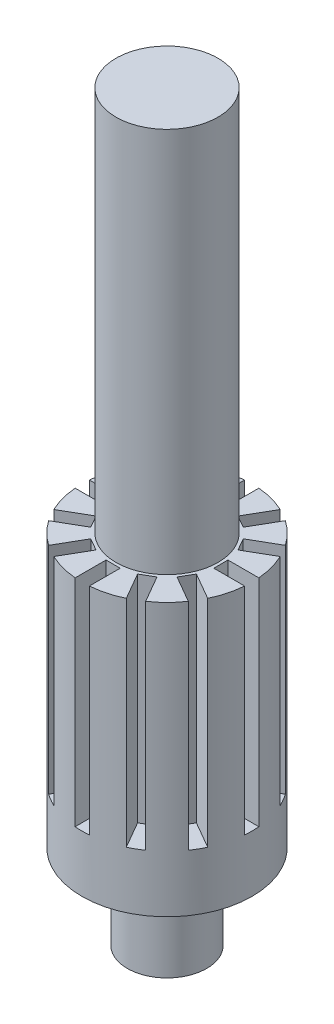
SolidWorks part; units mm, degrees
ref_plane "Front Plane" through (0, 0, 0) normal (0, 0, 1) x (1, 0, 0)
ref_plane "Top Plane" through (0, 0, 0) normal (0, 1, 0) x (1, 0, 0)
ref_plane "Right Plane" through (0, 0, 0) normal (1, 0, 0) x (0, 0, -1)
sketch "Sketch1" plane through (0, 0, 0) normal (0, 1, 0) x (1, 0, 0)
  circle A0 centre (0, 0) radius 15
  circle A1 centre (0, 0) radius 9
  point P4 (0, 0)
  dimension "D1" = 30
  dimension "D2" = 18
extrude "Boss-Extrude1" add sketch "Sketch1" against normal blind 48 contours A0 A1 | A1 region at (-14.5757, 0, 0) region at (0, 0, 0)
extrude "Boss-Extrude2" add sketch "Sketch1<4>" along normal blind 68 contours A1 region at (0, 0, 0)
sketch "Sketch1<4>" plane through (0, 0, 0) normal (0, 1, 0) x (1, 0, 0) same geometry as "Sketch1"
sketch "Sketch2" plane through (0, -48, 0) normal (0, -1, 0) x (1, 0, 0)
  circle A0 centre (0, 0) radius 7
  dimension "D1" = 14
extrude "Boss-Extrude3" add sketch "Sketch2" along normal blind 15
sketch "Sketch3" plane through (0, 0, 0) normal (0, 1, 0) x (1, 0, 0)
  line L1 (-1.25, 9.5) -> (1.25, 9.5)
  line L2 (-1.25, 9.5) -> (-1.25, 15.7102)
  line L3 (-1.25, 15.7102) -> (1.25, 15.7102)
  line L4 (1.25, 9.5) -> (1.25, 15.7102)
  point P4 (0, 9.5)
  point P6 (1.25, 15.7102)
  dimension "D1" = 2.5
  dimension "D2" = 9.5
extrude "Cut-Extrude1" cut sketch "Sketch3" against normal blind 38
pattern_circular "CirPattern1" count 12 over 360 about axis through (0, 0, 0) along (0, 1, 0) of "Cut-Extrude1"
sketch "Sketch4" plane through (0, -63, 0) normal (0, -1, 0) x (1, 0, 0)
  circle A0 centre (0, 0) radius 1.25
  dimension "D1" = 2.5
extrude "Cut-Extrude2" cut sketch "Sketch4" against normal up to surface (15 mm away) up to face at (0, -48, -7)
